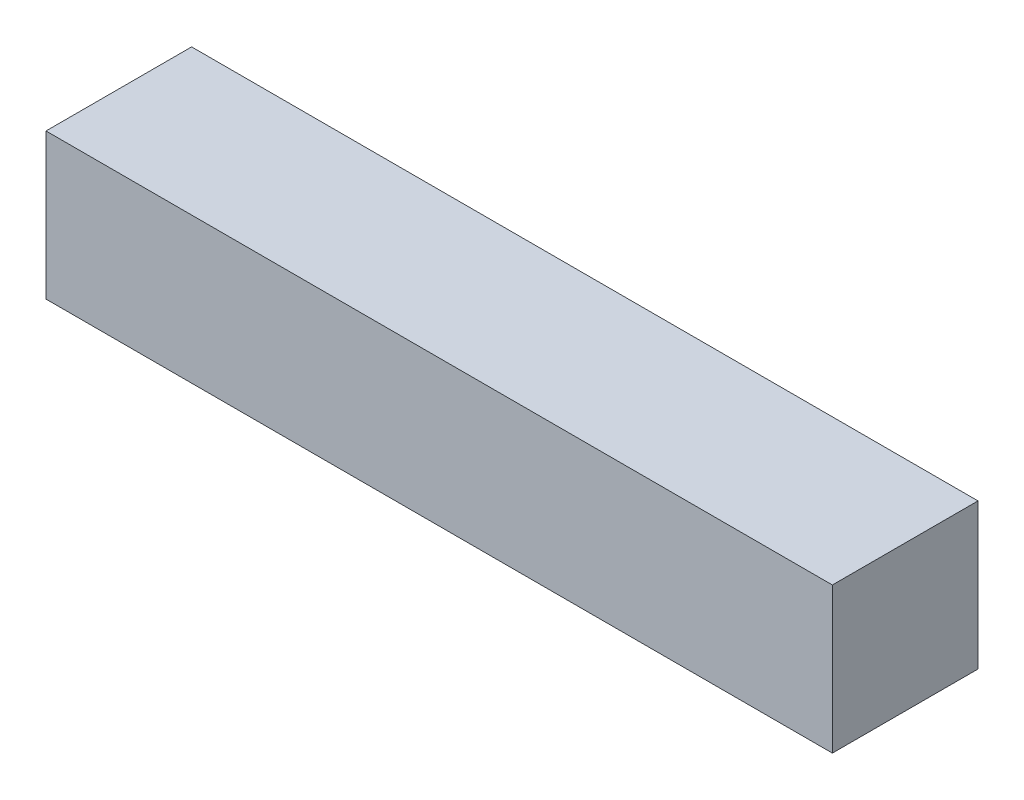
SolidWorks part; units mm, degrees
material "201 Annealed Stainless Steel (SS)"
ref_plane "Front Plane" through (0, 0, 0) normal (0, 0, 1) x (1, 0, 0)
ref_plane "Top Plane" through (0, 0, 0) normal (0, 1, 0) x (1, 0, 0)
ref_plane "Right Plane" through (0, 0, 0) normal (1, 0, 0) x (0, 0, -1)
sketch "Sketch1" plane through (0, 0, 0) normal (0, 0, 1) x (1, 0, 0)
  line L1 (-27, -5) -> (27, -5)
  line L2 (-27, -5) -> (-27, 5)
  line L3 (-27, 5) -> (27, 5)
  line L4 (27, -5) -> (27, 5)
  line L5 (-27, -5) -> (27, 5) construction
  line L6 (-27, 5) -> (27, -5) construction
  point P0 (0, 0)
  dimension "D1" = 54
  dimension "D2" = 10
extrude "Boss-Extrude1" add sketch "Sketch1" along normal mid plane 10
sketch "Sketch2" [suppressed] plane through (0, 0, 0) normal (0, 0, -1) x (-1, 0, 0)
  line L0 (61, 200) -> (61, -200) construction
  line L1 (-61, 314.7216) -> (-204.3993, 314.7216)
  line L2 (-61, 314.7216) -> (-61, -251.9618)
  line L3 (-61, -251.9618) -> (-204.3993, -251.9618)
  line L4 (-204.3993, 314.7216) -> (-204.3993, -251.9618)
  line L6 (61, 279.3211) -> (244.4765, 279.3211)
  line L7 (61, 279.3211) -> (61, -295.1839)
  line L8 (61, -295.1839) -> (244.4765, -295.1839)
  line L9 (244.4765, 279.3211) -> (244.4765, -295.1839)
  line L10 (-61, -200) -> (-61, -140) construction
extrude "Cut-Extrude1" [suppressed] cut sketch "Sketch2" against normal through all
sketch "Sketch3" [suppressed] plane through (49, 0, 0) normal (1, 0, 0) x (0, 0, -1)
  circle A0 centre (-6.722, 55.3681) radius 5.3835
surface "Surface-Extrude1" [suppressed] sketch "Sketch3"
sketch "Sketch4" [suppressed] plane through (-49, 0, 0) normal (-1, 0, 0) x (0, 0, 1)
  line L1 (2, 80) -> (0, 80) construction
  line L2 (0, -80) -> (0, 80) construction
  point P0 (7.5, 76)
  dimension "D1" = 4
  dimension "D2" = 7.5
ref_axis "Axis1" [suppressed] through (-49, 76, 7.5) along (1, 0, 0)
sketch "Sketch5" [suppressed] plane through (0, 0, 0) normal (0, 0, -1) x (-1, 0, 0)
  line L0 (49, 80) -> (49, -80) construction
  line L1 (-49, 80) -> (49, 80)
  line L2 (-49, 80) -> (-49, 60.2594)
  line L3 (-49, 60.2594) -> (49, 60.2594)
  line L4 (49, 80) -> (49, 60.2594)
extrude "Cut-Extrude2" [suppressed] cut sketch "Sketch5" against normal blind 3
sketch "Sketch6" [suppressed] plane through (0, 0, 2) normal (0, 0, 1) x (1, 0, 0)
  line L2 (0, -1.1) -> (0, 1.1) construction
  line L3 (-30, -15) -> (30, -15) construction
  circle A0 centre (0, -15) radius 20
  dimension "D1" = 40
extrude "Cut-Extrude3" [suppressed] cut sketch "Sketch6" against normal through all
